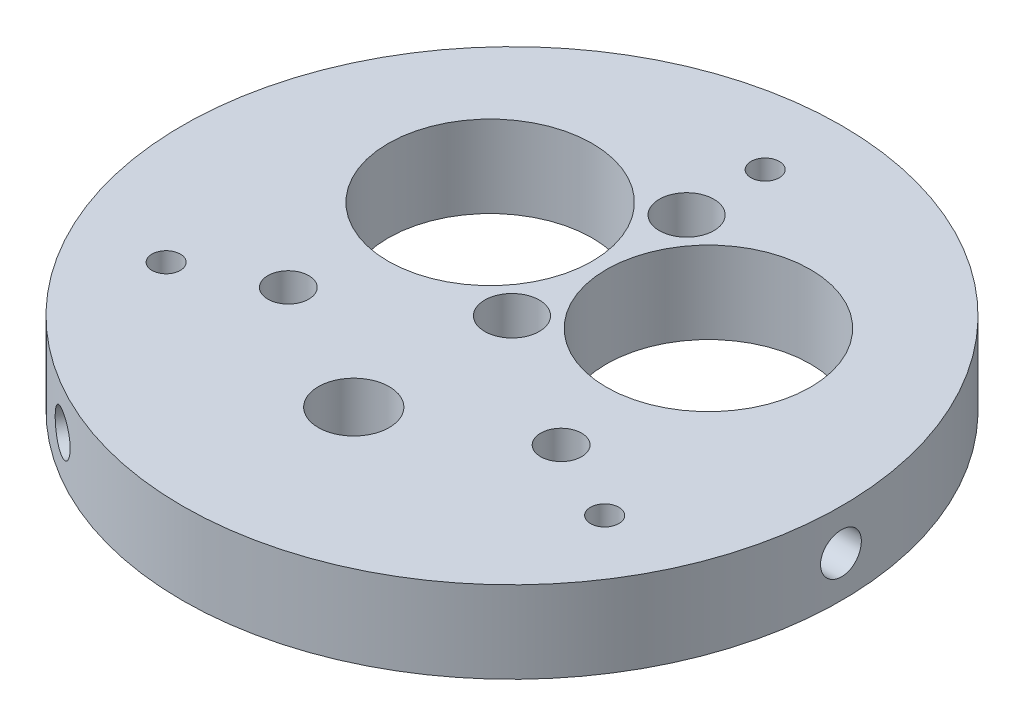
SolidWorks part; units mm, degrees
material "G10 Fiberglass"
ref_plane "Front Plane" through (0, 0, 0) normal (0, 0, 1) x (1, 0, 0)
ref_plane "Top Plane" through (0, 0, 0) normal (0, 1, 0) x (1, 0, 0)
ref_plane "Right Plane" through (0, 0, 0) normal (1, 0, 0) x (0, 0, -1)
sketch "Sketch1" plane through (0, 0, 0) normal (0, 1, 0) x (1, 0, 0)
  circle A0 centre (0, 0) radius 38.354
  dimension "D1" = 76.708
extrude "Boss-Extrude1" add sketch "Sketch1" along normal blind 9.525
sketch "Sketch2" plane through (0, 9.525, 0) normal (0, 1, 0) x (1, 0, 0)
  line L0 (12.7, 10.16) -> (-12.7, 10.16) construction
  line L3 (0, 6.35) -> (0, -19.05) construction
  line L4 (-14.6936, 35.4278) -> (-10.8624, 36.7836) construction
  line L5 (-14.6936, 35.4278) -> (-12.0454, 27.9451) construction
  line L6 (-10.8624, 36.7836) -> (-8.2143, 29.3009) construction
  line L7 (-12.0454, 27.9451) -> (-8.2143, 29.3009) construction
  line L8 (37.9022, -4.9723) -> (30.0979, -3.5244) construction
  line L9 (37.9022, -4.9723) -> (37.1609, -8.9682) construction
  line L10 (37.1609, -8.9682) -> (29.3566, -7.5202) construction
  line L11 (30.0979, -3.5244) -> (29.3566, -7.5202) construction
  line L12 (-23.3832, -30.3216) -> (-18.2271, -24.2869) construction
  line L13 (-23.3832, -30.3216) -> (-26.473, -27.6817) construction
  line L14 (-26.473, -27.6817) -> (-21.3169, -21.6469) construction
  line L15 (-18.2271, -24.2869) -> (-21.3169, -21.6469) construction
  line L16 (0, 10.16) -> (0, -18.415) construction
  line L17 (-12.7, 10.16) -> (12.7, 10.16) construction
  line L18 (-12.7, 24.13) -> (12.7, 24.13) construction
  line L19 (-12.7, -3.81) -> (12.7, -3.81) construction
  circle A0 centre (0, 0) radius 29.464 construction
  circle A1 centre (0, 29.464) radius 1.651
  circle A2 centre (25.5166, -14.732) radius 1.651
  circle A3 centre (-25.5166, -14.732) radius 1.651
  circle A4 centre (0, -18.415) radius 4.1275
  circle A7 centre (0, 0) radius 38.354 construction
  circle A8 centre (-12.7, 10.16) radius 11.8745
  circle A9 centre (12.7, 10.16) radius 11.8745
  circle A10 centre (0, 20.32) radius 3.175
  circle A11 centre (0, 0) radius 3.175
  arc A12 (-12.7, 24.13) -> (-12.7, -3.81) centre (-12.7, 10.16) ccw construction
  arc A13 (12.7, -3.81) -> (12.7, 24.13) centre (12.7, 10.16) ccw construction
  point P11 (0, 0)
  point P36 (-0.0582, 0.0446)
  point P38 (0, 10.16)
  dimension "D1" = 3.302
  dimension "D2" = 58.928
  dimension "D11" = 8.255
  dimension "D4" = 23.749
  dimension "D5" = 23.749
  dimension "D13" = 6.35
  dimension "D14" = 6.35
  dimension "D7" = 4.064
  dimension "D8" = 7.9375
  dimension "D6" = 10.16
  dimension "D10" = 25.4
  dimension "D12" = 28.575
  dimension "D15" = 27.94
  dimension "D17" = 3.81
  dimension "D16" = 3.81
  dimension "D3" = 3
  dimension "D9" = 3
extrude "Cut-Extrude1" cut sketch "Sketch2" against normal through all contours A1 | A3 | A2 | A4 | A8 | A9 | A10 | A11 region at (0, 9.525, -29.464) region at (25.5166, 9.525, 14.732) region at (-25.5166, 9.525, 14.732) region at (0, 9.525, 18.415) region at (-12.7, 9.525, -10.16) region at (12.7, 9.525, -10.16) region at (0, 9.525, -20.32) region at (0, 9.525, 0)
ref_plane "Plane1" through (-19.177, 0, -33.2155) normal (-0.5, 0, -0.866) x (0, -1, 0)
sketch "Sketch4" plane through (-19.177, 0, -33.2155) normal (-0.5, 0, -0.866) x (0, -1, 0)
  circle A0 centre (-4.7625, 0) radius 2.3749
  dimension "D1" = 4.7625
  dimension "D2" = 4.7498
extrude "Cut-Extrude2" cut sketch "Sketch4" against normal blind 6.35
ref_axis "Axis1" through (0, 10.0012, 0) along (0, -1, 0)
pattern_circular "CirPattern1" count 3 over 360 about axis through (0, 10.0012, 0) along (0, -1, 0) of "Cut-Extrude2"
pattern_circular "CirPattern2" [suppressed] count 2 over 360 about axis through (0, 10.0012, 0) along (0, -1, 0) of bodies 104
sketch "Sketch5" plane through (0, 9.525, 0) normal (0, 1, 0) x (1, 0, 0)
  line L0 (-15.875, -10.16) -> (15.875, -10.16) construction
  line L1 (0, 0) -> (0, -10.16) construction
  circle A0 centre (-15.875, -10.16) radius 2.3813
  circle A1 centre (15.875, -10.16) radius 2.3813
  dimension "D1" = 4.7625
  dimension "D2" = 4.7625
  dimension "D3" = 31.75
  dimension "D4" = 10.16
extrude "Cut-Extrude3" cut sketch "Sketch5" against normal through all both
equation "\"D5@Sketch2\"=\"D4@Sketch2\""
equation "\"D4@Sketch2\"=0.925in+0.01"
equation "\"D13@Sketch2\"=\"D14@Sketch2\""
equation "\"D16@Sketch2\"=\"D17@Sketch2\""
